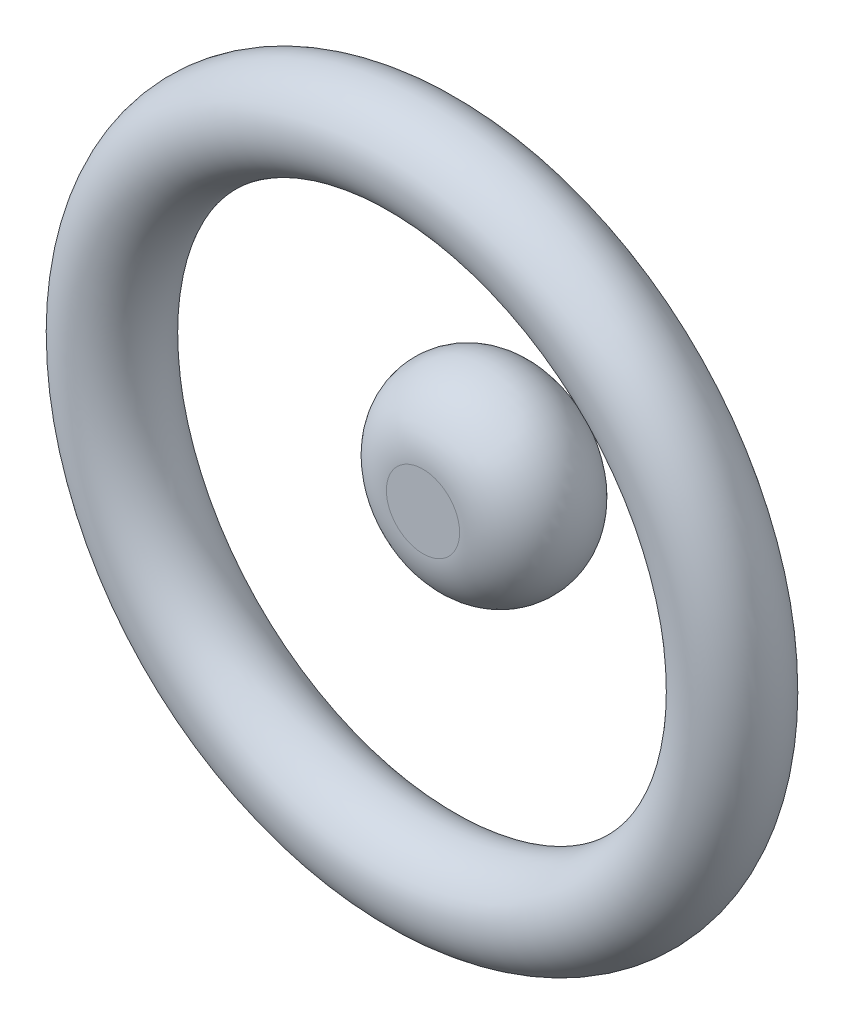
SolidWorks part; units mm, degrees
other "steering wheel"
other "hub"
ref_plane "Front" through (0, 0, 0) normal (0, 0, 1) x (1, 0, 0)
ref_plane "Top" through (0, 0, 0) normal (0, 1, 0) x (1, 0, 0)
ref_plane "Right" through (0, 0, 0) normal (1, 0, 0) x (0, 0, -1)
other "Configuration Table"
sketch "Sketch1" plane through (0, 0, 0) normal (1, 0, 0) x (0, 0, -1)
  line L0 (-25, 0) -> (25, 0)
  line L1 (25, 15) -> (25, 0)
  line L2 (-25, 0) -> (-25, 15)
  line L3 (-113.5969, 0) -> (93.7779, 0) construction
  arc A0 (-25, 15) -> (25, 15) centre (0, 15) cw
  circle A1 centre (-25.4, 127) radius 19.05
  point P8 (0, 0)
  dimension "D1" = 38.1
  dimension "D5" = 25
  dimension "D2" = 25.4
  dimension "D3" = 127
  dimension "D4" = 15
revolve "Revolve1" add sketch "Sketch1" angle 360 about L3
ref_axis "Axis1" through (0, 0, -54.8614) along (0, 0, 1)
sketch "Sketch2" plane through (0, 0, 0) normal (0, 1, 0) x (1, 0, 0)
  line L1 (-16.51, -3.175) -> (16.51, -3.175)
  line L2 (-19.05, -0.635) -> (-19.05, 0.635)
  line L3 (-16.51, 3.175) -> (16.51, 3.175)
  line L4 (19.05, -0.635) -> (19.05, 0.635)
  arc A0 (16.51, 3.175) -> (19.05, 0.635) centre (16.51, 0.635) cw
  arc A1 (16.51, -3.175) -> (19.05, -0.635) centre (16.51, -0.635) ccw
  arc A2 (-16.51, -3.175) -> (-19.05, -0.635) centre (-16.51, -0.635) cw
  arc A3 (-19.05, 0.635) -> (-16.51, 3.175) centre (-16.51, 0.635) cw
  point P4 (19.05, 0)
  point P5 (0, 3.175)
  point P8 (19.05, 3.175)
  point P11 (19.05, -3.175)
  point P16 (-19.05, 3.175)
  dimension "D3" = 2.54
  dimension "D1" = 38.1
  dimension "D2" = 6.35
sketch "Sketch3" plane through (0, 0, 0) normal (1, 0, 0) x (0, 0, -1)
  spline_without_curve S0
  dimension "D1" = 25.4
  dimension "D2" = 127
